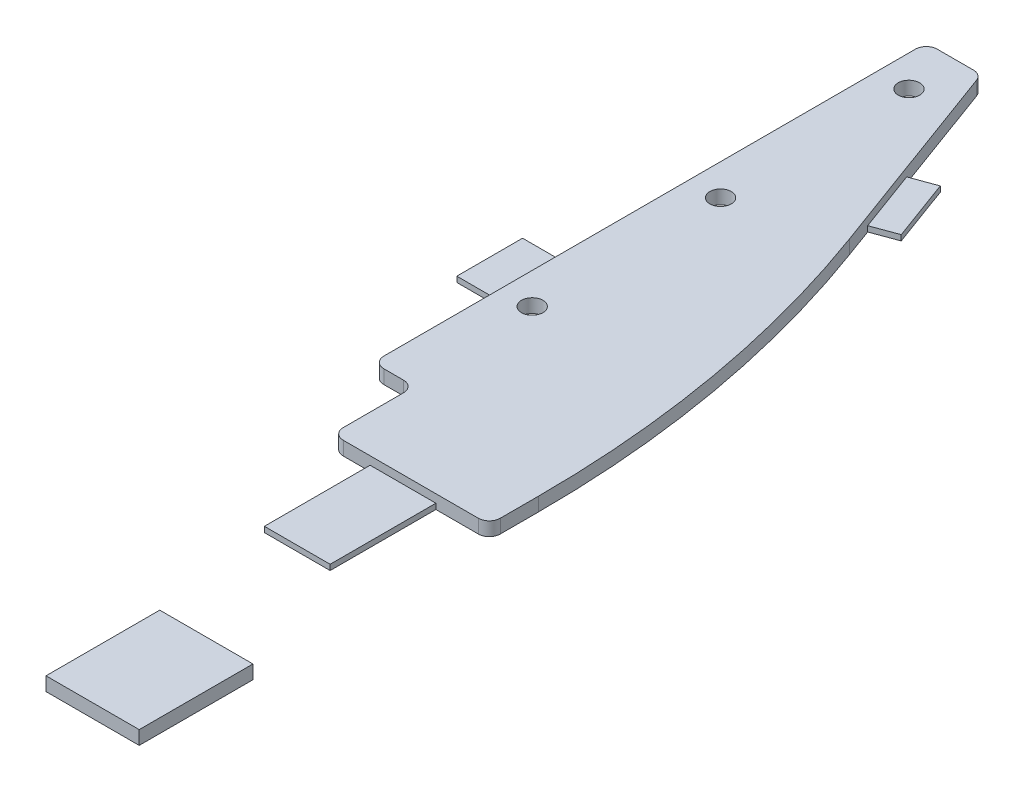
SolidWorks part; units mm, degrees
material "ABS PC"
ref_plane "Front Plane" through (0, 0, 0) normal (0, 0, 1) x (1, 0, 0)
ref_plane "Top Plane" through (0, 0, 0) normal (0, 1, 0) x (1, 0, 0)
ref_plane "Right Plane" through (0, 0, 0) normal (1, 0, 0) x (0, 0, -1)
sketch "Sketch1" plane through (0, 0, 0) normal (0, 1, 0) x (1, 0, 0)
  line L0 (0, 117.357) -> (0, -44.3349) construction
  line L1 (-203.073, 0) -> (-166.6875, 0)
  line L2 (-166.6875, 0) -> (-166.6875, 11.43)
  line L3 (-182.2884, 99.0764) -> (-200.025, 147.32)
  line L4 (-212.725, 147.32) -> (-212.725, 19.05)
  line L5 (-212.725, 19.05) -> (-203.073, 19.05)
  line L6 (-203.073, 19.05) -> (-203.073, 0)
  line L7 (-200.025, 147.32) -> (-212.725, 147.32)
  arc A0 (-166.6875, 11.43) -> (-182.2884, 99.0764) centre (-420.6875, 11.43) ccw
  dimension "D6" = 12.7
  dimension "D7" = 254
  dimension "D1" = 425.45
  dimension "D2" = 333.375
  dimension "D3" = 19.05
  dimension "D4" = 9.652
  dimension "D5" = 147.32
  dimension "D8" = 11.43
base flange "Base-Flange1" sketch "Sketch1" thickness 3.175 reverse thickness direction no parameters "D1"=0.7366
fillet "Fillet1" radius 2.54 6 edges at (-203.073, -1.5875, -19.05) (-212.725, -1.5875, -147.32) (-200.025, -1.5875, -147.32) (-212.725, -1.5875, -19.05) (-166.6875, -1.5875, 0) (-203.073, -1.5875, 0)
sketch "Sketch9" plane through (0, 0, 0) normal (0, 1, 0) x (1, 0, 0)
  line L0 (-212.725, 144.78) -> (-212.725, 21.59) construction
  line L2 (-201.7974, 147.32) -> (-210.185, 147.32) construction
  circle A0 centre (-205.486, 5.08) radius 2.4892 construction
  circle A1 centre (-205.486, 48.7362) radius 2.4892
  circle A2 centre (-205.486, 92.3925) radius 2.4892
  circle A3 centre (-205.486, 136.0487) radius 2.4892
  dimension "D1" = 7.239
  dimension "D2" = 11.2713
  dimension "D3" = 4.9784
  dimension "D5" = 43.6562
  dimension "D4" = 4
extrude "Cut-Extrude1" cut sketch "Sketch9" against normal through all normal cut yes
sketch "Bend-Lines1" plane through (0, 0, 0) normal (0, 1, 0) x (1, 0, 0)
sketch "Bounding-Box1" plane through (0, 0, 0) normal (0, 1, 0) x (1, 0, 0)
sketch "Sketch10" plane through (0, 0, 0) normal (0, 1, 0) x (1, 0, 0)
  line L1 (-166.0998, -55.3629) -> (-187.7014, -55.3629)
  line L2 (-166.0998, -55.3629) -> (-166.0998, -81.7207)
  line L3 (-166.0998, -81.7207) -> (-187.7014, -81.7207)
  line L4 (-187.7014, -55.3629) -> (-187.7014, -81.7207)
  line L5 (-166.0998, -55.3629) -> (-187.7014, -81.7207) construction
  line L6 (-166.0998, -81.7207) -> (-187.7014, -55.3629) construction
  point P4 (-176.9006, -68.5418)
extrude "Boss-Extrude1" add sketch "Sketch10" against normal up to surface (3.175 mm away) separate body up to face at (-205.486, -3.175, -46.247)
sketch "Sketch11" plane through (0, -3.175, 0) normal (0, -1, 0) x (1, 0, 0)
  line L0 (-194.3078, 0) -> (-179.0678, 0)
  line L1 (-194.3078, 0) -> (-194.3078, 24.507)
  line L2 (-179.0678, 0) -> (-179.0678, 24.507)
  line L3 (-194.3078, 24.507) -> (-179.0678, 24.507)
  line L5 (-212.725, -63.2334) -> (-212.725, -47.9934)
  line L6 (-212.725, -63.2334) -> (-222.2137, -63.2334)
  line L7 (-212.725, -47.9934) -> (-222.2137, -47.9934)
  line L8 (-222.2137, -63.2334) -> (-222.2137, -47.9934)
  line L9 (-212.725, -144.78) -> (-212.725, -21.59) construction
  line L10 (-184.7366, -105.7354) -> (-189.9954, -120.0394)
  line L11 (-184.7366, -105.7354) -> (-179.0457, -107.8277)
  line L12 (-189.9954, -120.0394) -> (-184.3045, -122.1316)
  line L13 (-179.0457, -107.8277) -> (-184.3045, -122.1316)
  line L14 (-182.2884, -99.0764) -> (-199.4134, -145.6565) construction
  line L17 (-200.533, 0) -> (-169.2275, 0) construction
  line L18 (-182.2884, -99.0764) -> (-199.4134, -145.6565) construction
  point P14 (-189.9954, -120.0394)
  dimension "D1" = 15.24
extrude "Boss-Extrude2" add sketch "Sketch11" against normal blind 1.27
sheet metal parameters "Sheet-Metal2" thickness 3.175 parameters "D1"=0.7366
flat pattern "Flat-Pattern2"
sketch "Bend-Lines2" plane through (0, 0, 0) normal (0, 1, 0) x (1, 0, 0)
sketch3d "Bounding-Box2"
  line L0 (209.55, 135.89, 0) -> (209.55, -12.7, 0) construction
  line L1 (254, 135.89, 0) -> (254, -12.7, 0) construction
  line L2 (209.55, 135.89, 0) -> (254, 135.89, 0) construction
  line L3 (209.55, -12.7, 0) -> (254, -12.7, 0) construction
sheet metal parameters "Sheet-Metal4" thickness 3.175 parameters "D1"=0.7366
flat pattern "Flat-Pattern2"
sketch "Bend-Lines2" plane through (0, 0, 0) normal (0, 1, 0) x (1, 0, 0)
sketch3d "Bounding-Box2"
  line L0 (207.9625, 135.89, 0) -> (207.9625, -11.43, 0) construction
  line L1 (254, 135.89, 0) -> (254, -11.43, 0) construction
  line L2 (207.9625, 135.89, 0) -> (254, 135.89, 0) construction
  line L3 (207.9625, -11.43, 0) -> (254, -11.43, 0) construction
